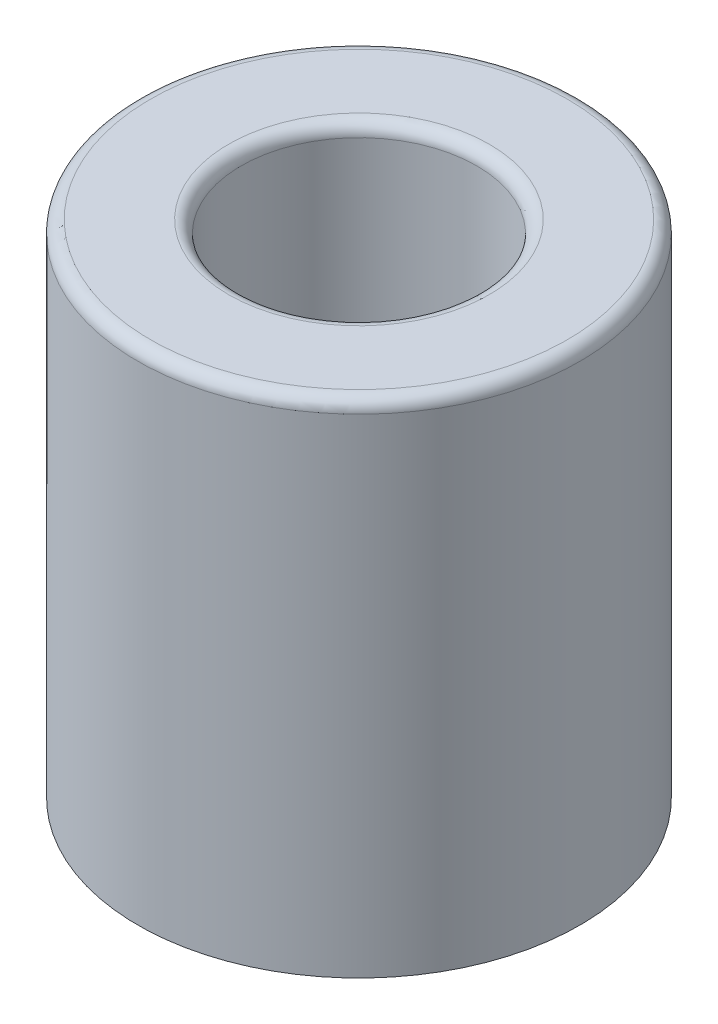
SolidWorks part; units mm, degrees
material "Rubber"
ref_plane "Front" through (0, 0, 0) normal (0, 0, 1) x (1, 0, 0)
ref_plane "Top" through (0, 0, 0) normal (0, 1, 0) x (1, 0, 0)
ref_plane "Right" through (0, 0, 0) normal (1, 0, 0) x (0, 0, -1)
sketch "Sketch1" plane through (0, 0, 0) normal (0, 0, 1) x (1, 0, 0)
  line L0 (5.9531, 0) -> (-5.9531, 0) construction
  line L1 (0, 0) -> (0, 13.4937) construction
  line L2 (3.175, 4.7625) -> (-3.175, 4.7625) construction
  line L3 (1.7859, 0) -> (-1.7859, 0) construction
  point P7 (0, 4.7625)
  dimension "OD" = 11.9062
  dimension "Height" = 13.4937
  dimension "Counterbore Dia" = 6.35
  dimension "Mounting Surface Ht" = 4.7625
  dimension "Mounting Hole Dia" = 3.5719
sketch "Sketch2" plane through (0, 0, 0) normal (0, 0, 1) x (1, 0, 0)
  line L0 (-5.9531, 0) -> (-5.9531, 13.1564)
  line L1 (-5.6158, 13.4937) -> (-3.175, 13.4937)
  line L2 (-3.175, 13.4937) -> (-3.175, 4.7625)
  line L3 (-3.175, 4.7625) -> (-1.7859, 4.7625)
  line L4 (3.175, 4.7625) -> (-3.175, 4.7625) construction
  line L5 (-1.7859, 4.7625) -> (-1.7859, 0)
  line L6 (-1.7859, 0) -> (-5.9531, 0)
  arc A0 (-5.6158, 13.4937) -> (-5.9531, 13.1564) centre (-5.6158, 13.1564) ccw
  dimension "D1" = 0.3373
revolve "Revolve1" add sketch "Sketch2" angle 360 about L1
fillet "Fillet1" radius 0.3373 1 edges at (0, 13.4937, -3.175)
sketch "Sketch3" plane through (0, 0, 0) normal (0, 0, 1) x (1, 0, 0)
  line L0 (-1.7859, 4.7625) -> (-1.7859, 0) construction
  line L1 (1.7859, 0) -> (1.7859, 4.7625) construction
  line L2 (-3.175, 13.1564) -> (-3.175, 4.7625) construction
  line L3 (3.175, 4.7625) -> (3.175, 13.1564) construction
  line L4 (-1.7859, 4.7625) -> (-1.7859, 0)
  line L5 (1.7859, 0) -> (1.7859, 4.7625)
  line L6 (-3.175, 13.1564) -> (-3.175, 4.7625)
  line L7 (3.175, 4.7625) -> (3.175, 13.1564)
  line L8 (-3.175, 4.7625) -> (-1.7859, 4.7625)
  line L9 (1.7859, 4.7625) -> (3.175, 4.7625)
  arc A0 (-3.175, 13.1564) -> (-3.5123, 13.4937) centre (-3.5123, 13.1564) ccw construction
  arc A1 (3.5123, 13.4937) -> (3.175, 13.1564) centre (3.5123, 13.1564) ccw construction
  arc A2 (-3.175, 13.1564) -> (-3.5123, 13.4937) centre (-3.5123, 13.1564) ccw
  arc A3 (3.5123, 13.4937) -> (3.175, 13.1564) centre (3.5123, 13.1564) ccw
ref_plane "Contact Surface 1" through (0, 0, 0) normal (0, -1, 0) x (-1, 0, 0)
ref_axis "Center Axis1" through (0, 6.6675, 0) along (0, -1, 0)
equation "\"D1@Sketch2\"=\"Height@Sketch1\"*.025"
equation "\"D1@Fillet1\"=\"D1@Sketch2\""
